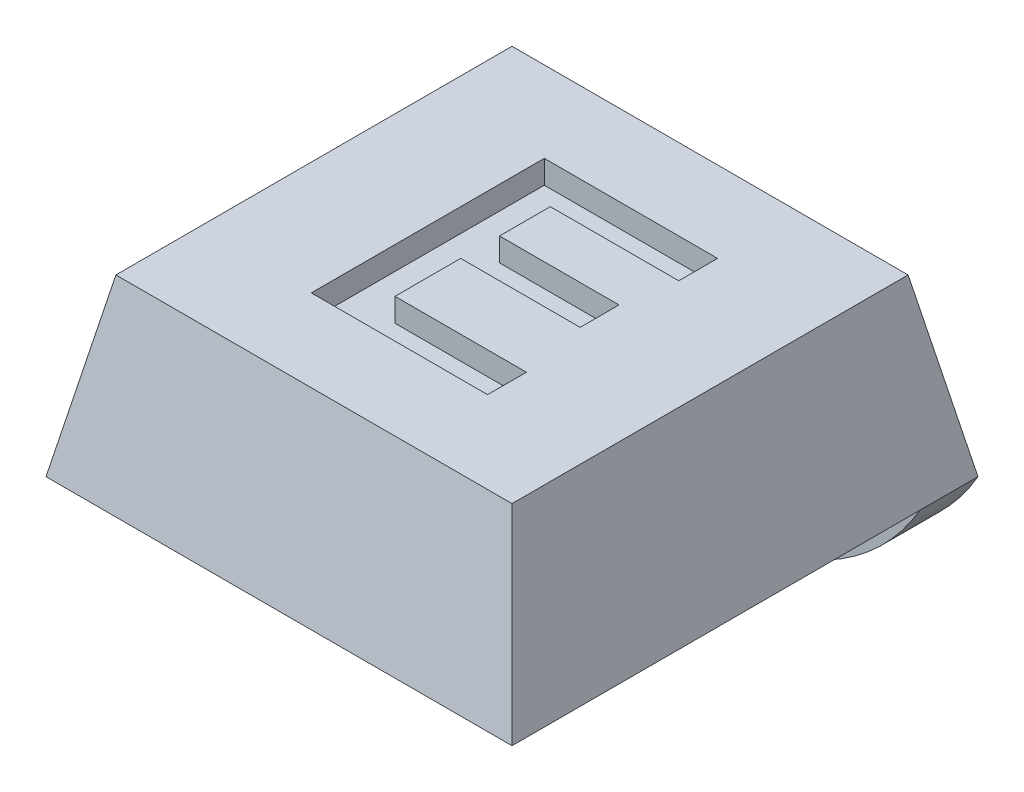
SolidWorks part; units mm, degrees
ref_plane "Front Plane" through (0, 0, 0) normal (0, 0, 1) x (1, 0, 0)
ref_plane "Top Plane" through (0, 0, 0) normal (0, 1, 0) x (1, 0, 0)
ref_plane "Right Plane" through (0, 0, 0) normal (1, 0, 0) x (0, 0, -1)
sketch "Sketch1" plane through (0, 0, 0) normal (0, 1, 0) x (1, 0, 0)
  line L1 (0, 0) -> (8, 0)
  line L2 (0, 0) -> (0, 8)
  line L3 (0, 8) -> (8, 8)
  line L4 (8, 0) -> (8, 8)
  dimension "D1" = 8
  dimension "D2" = 8
extrude "Boss-Extrude1" add sketch "Sketch1" along normal blind 3
sketch "Sketch2" plane through (0, 0, 0) normal (0, 0, 1) x (1, 0, 0)
  line L0 (0, 0) -> (0.6, 3)
  line L1 (0, 3) -> (8, 3) construction
  line L2 (0.6, 3) -> (0, 3)
  line L3 (0, 3) -> (0, 0)
  line L4 (8, 0) -> (7.4, 3)
  line L5 (7.4, 3) -> (8, 3)
  line L6 (8, 3) -> (8, 0)
  dimension "D1" = 0.6
  dimension "D2" = 0.6
extrude "Cut-Extrude1" cut sketch "Sketch2" against normal through all both and the other way through all
sketch "Sketch3" plane through (0, 0, 0) normal (1, 0, 0) x (0, 0, -1)
  line L0 (0, 0) -> (0.6, 3)
  line L1 (8, 3) -> (0, 3) construction
  line L2 (0.6, 3) -> (0, 3)
  line L3 (0, 3) -> (0, 0)
  line L4 (8, 3) -> (7.4, 3)
  line L5 (7.4, 3) -> (8, 0)
  line L6 (8, 3) -> (8, 0)
  dimension "D1" = 0.6
  dimension "D2" = 0.6
extrude "Cut-Extrude2" cut sketch "Sketch3" along normal blind 11
sketch "Sketch4" plane through (0, 0, 0) normal (0, -1, 0) x (1, 0, 0)
  line L0 (8, 0) -> (8, -8) construction
  line L3 (0, 0) -> (8, 0) construction
  circle A0 centre (4, -3.75) radius 1.8
  dimension "D1" = 3.6
  dimension "D2" = 4
  dimension "D3" = 3.75
extrude "Cut-Extrude3" cut sketch "Sketch4" against normal blind 0.8
sketch "Sketch5" plane through (0, 0, 0) normal (0, -1, 0) x (1, 0, 0)
  line L0 (8, 0) -> (8, -8) construction
  line L1 (0, -8) -> (8, -8)
  line L2 (0, -8) -> (0, -7)
  line L3 (0, -7) -> (8, -7)
  line L4 (8, -8) -> (8, -7)
  dimension "D1" = 1
extrude "Boss-Extrude2" add sketch "Sketch5" along normal blind 2
fillet "Fillet1" radius 4 2 edges at (8, -2, -7.5) (0, -2, -7.5)
sketch "Sketch6" plane through (0, 3, 0) normal (0, 1, 0) x (1, 0, 0)
  text T0 "E" font "Arial" height 4
extrude "Cut-Extrude4" cut sketch "Sketch6" against normal blind 0.4
